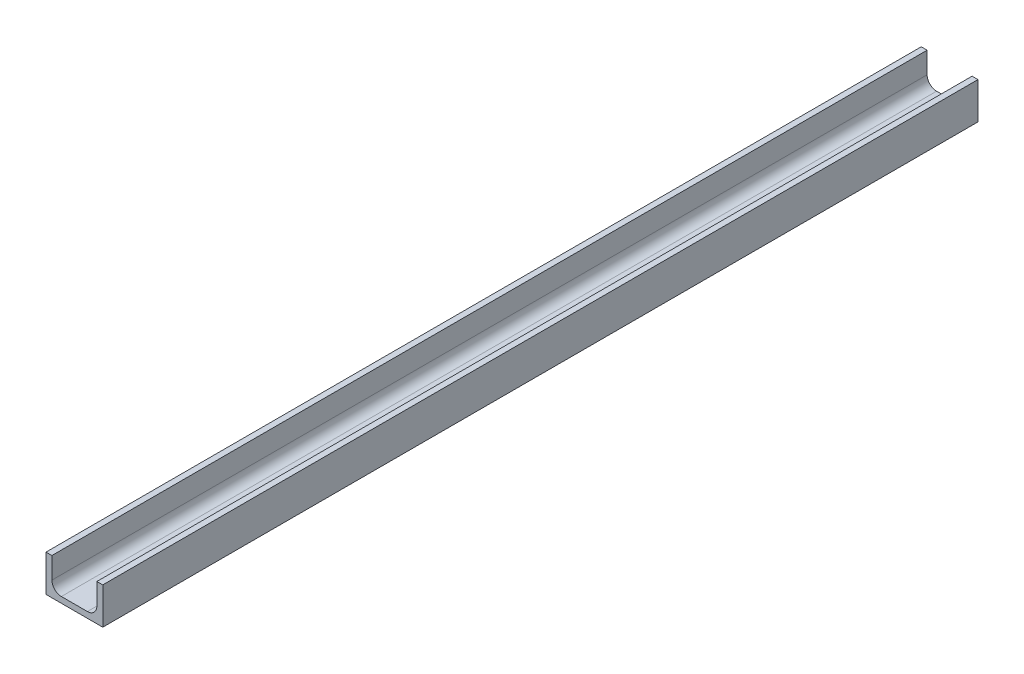
SolidWorks part; units mm, degrees
material "Alloy Steel"
ref_plane "Front Plane" through (0, 0, 0) normal (0, 0, 1) x (1, 0, 0)
ref_plane "Top Plane" through (0, 0, 0) normal (0, 1, 0) x (1, 0, 0)
ref_plane "Right Plane" through (0, 0, 0) normal (1, 0, 0) x (0, 0, -1)
sketch "Sketch113" plane through (0, 0, 0) normal (0, 0, 1) x (1, 0, 0)
  line L0 (0, 0) -> (0, 49.2252)
  line L1 (0, 49.2252) -> (7.9248, 49.2252)
  line L2 (7.9248, 49.2252) -> (7.9248, 20.6248)
  line L3 (20.6248, 7.9248) -> (55.5752, 7.9248)
  line L4 (68.2752, 20.6248) -> (68.2752, 49.2252)
  line L5 (68.2752, 49.2252) -> (76.2, 49.2252)
  line L6 (76.2, 49.2252) -> (76.2, 0)
  line L7 (76.2, 0) -> (0, 0)
  arc A0 (68.2752, 20.6248) -> (55.5752, 7.9248) centre (55.5752, 20.6248) cw
  arc A1 (7.9248, 20.6248) -> (20.6248, 7.9248) centre (20.6248, 20.6248) ccw
  dimension "D6" = 12.7
  dimension "D1" = 76.2
  dimension "D2" = 49.2252
  dimension "D3" = 7.9248
  dimension "D4" = 7.9248
  dimension "D5" = 7.9248
extrude "Boss-Extrude1" add sketch "Sketch113" along normal blind 1174.75
sketch "Sketch114" plane through (0, 0, 0) normal (0, -1, 0) x (1, 0, 0)
  line L0 (38.1, 0) -> (38.1, 1174.75) construction
  line L1 (0, 0) -> (76.2, 0) construction
  line L2 (0, 1174.75) -> (76.2, 1174.75) construction
  line L3 (0, 587.375) -> (76.2, 587.375) construction
  line L4 (0, 1174.75) -> (0, 0) construction
  line L5 (76.2, 1174.75) -> (76.2, 0) construction
  circle A0 centre (38.1, 206.375) radius 6.35
  circle A1 centre (38.1, 968.375) radius 6.35
  dimension "D1" = 12.7
  dimension "D2" = 762
  dimension "D3" = 381
hole_wizard "1/2 Clearance Hole1" positions "3DSketch1" profile "Sketch115" hole size "1/2" standard "ANSI Inch" end condition through all
sketch3d "3DSketch1"
  point P0 (38.1, 0, 206.375)
  point P3 (38.1, 0, 968.375)
sketch "Sketch115" plane through (38.1, 0, 206.375) normal (1, 0, 0) x (0, 0, -1)
  line L0 (0, 0) -> (0, 49.2252)
  line L1 (0, 49.2252) -> (6.5481, 49.2252)
  line L2 (6.5481, 49.2252) -> (6.5481, 0)
  line L5 (6.5481, 0) -> (0, 0)
  line L11 (0, -6.35) -> (0, 107.95) construction
  dimension "Thru Hole Dia." = 13.0962
  dimension "Thru Hole Depth" = 49.2252
sketch "Sketch116" plane through (0, 0, 0) normal (0, -1, 0) x (1, 0, 0)
  circle A0 centre (38.1, 968.375) radius 25.146
  circle A1 centre (38.1, 206.375) radius 25.146
  circle A2 centre (38.1, 206.375) radius 6.5481 construction
  circle A3 centre (38.1, 206.375) radius 6.5481
  circle A4 centre (38.1, 968.375) radius 6.5481 construction
  circle A5 centre (38.1, 968.375) radius 6.5481
  dimension "D1" = 50.292
extrude "Boss-Extrude2" add sketch "Sketch116" along normal blind 4.953
